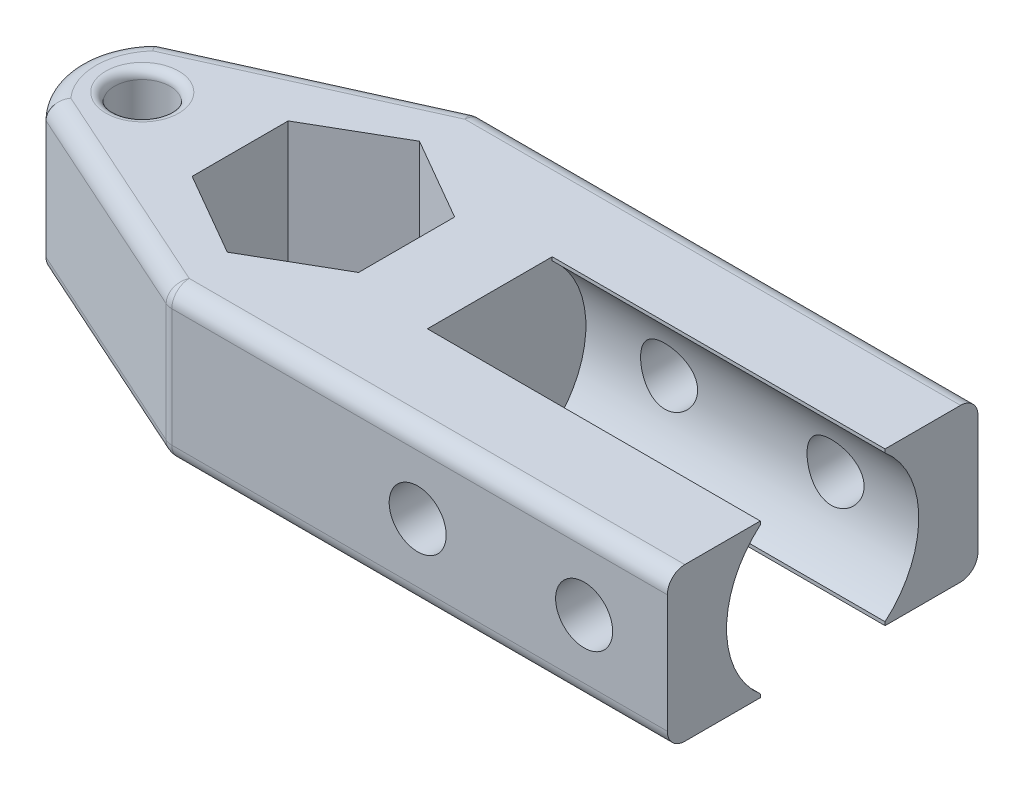
SolidWorks part; units mm, degrees
ref_plane "Front Plane" through (0, 0, 0) normal (0, 0, 1) x (1, 0, 0)
ref_plane "Top Plane" through (0, 0, 0) normal (0, 1, 0) x (1, 0, 0)
ref_plane "Right Plane" through (0, 0, 0) normal (1, 0, 0) x (0, 0, -1)
sketch "Sketch2" plane through (0, 0, 0) normal (0, 1, 0) x (1, 0, 0)
  line L0 (41.275, 0) -> (-41.275, 0) construction
  line L1 (31.75, -17.78) -> (-25.4, -17.78)
  line L3 (31.75, 17.78) -> (-25.4, 17.78)
  line L4 (-41.275, 0) -> (-60.325, 0) construction
  line L5 (41.275, -17.78) -> (-41.275, 17.78) construction
  line L6 (41.275, 17.78) -> (-41.275, -17.78) construction
  line L7 (-25.4, 17.78) -> (-25.4, -17.78) construction
  line L8 (31.75, 17.78) -> (31.75, -17.78)
  line L9 (-25.4, 10.9985) -> (-34.925, 5.4993)
  line L10 (-34.925, 5.4993) -> (-34.925, -5.4993)
  line L11 (-34.925, -5.4993) -> (-25.4, -10.9985)
  line L12 (-25.4, -10.9985) -> (-15.875, -5.4993)
  line L13 (-15.875, -5.4993) -> (-15.875, 5.4993)
  line L14 (-15.875, 5.4993) -> (-25.4, 10.9985)
  line L15 (-50.8, 6.35) -> (-25.4, 17.78)
  line L16 (-25.4, -17.78) -> (-50.8, -6.35)
  circle A0 centre (-25.4, 0) radius 9.525 construction
  arc A1 (-50.8, -6.35) -> (-50.8, 6.35) centre (-44.45, 0) cw
  circle A2 centre (-46.1277, 0) radius 3.175
  point P0 (0, 0)
  point P21 (-50.8, 0)
  dimension "D4" = 25.4
  dimension "D5" = 57.15
  dimension "D1" = 35.56
  dimension "D2" = 82.55
  dimension "D3" = 15.875
extrude "Boss-Extrude1" add sketch "Sketch2" along normal blind 17.526 contours A1 L16 L1 L3 L15 A2 region at (-3.1953, 0, 0)
fillet "Fillet4" radius 1 2 edges at (-46.1277, 0, 3.175) (-46.1277, 17.526, 3.175)
fillet "Fillet7" radius 2 6 edges at (-53.4303, 0, 0) (-38.1, 0, -12.065) (-38.1, 0, 12.065) (-38.1, 17.526, -12.065) (-53.4303, 17.526, 0) (-38.1, 17.526, 12.065)
sketch "Sketch5" plane through (31.75, 0, 0) normal (1, 0, 0) x (0, 0, -1)
  line L0 (-17.78, 8.763) -> (17.78, 8.763) construction
  line L1 (-17.78, 17.526) -> (-17.78, 0) construction
  line L2 (17.78, 17.526) -> (17.78, 0) construction
  line L3 (7.1438, 17.1276) -> (7.1438, 20.263)
  line L4 (7.1438, -2.737) -> (-7.1437, -2.737)
  line L5 (7.1438, -2.737) -> (7.1438, 0.3984)
  line L6 (7.1438, 20.263) -> (-7.1437, 20.263)
  line L7 (-7.1437, -2.737) -> (-7.1437, 0.3984)
  line L8 (7.1438, -2.737) -> (-7.1437, 20.263) construction
  line L9 (7.1438, 20.263) -> (-7.1437, -2.737) construction
  line L10 (-7.1437, 17.1276) -> (-7.1437, 20.263)
  arc A0 (-7.1437, 17.1276) -> (-7.1437, 0.3984) centre (0, 8.763) ccw
  arc A1 (7.1438, 0.3984) -> (7.1438, 17.1276) centre (0, 8.763) ccw
  dimension "D1" = 14.2875
  dimension "D2" = 11
extrude "Cut-Extrude3" cut sketch "Sketch5" against normal blind 38.1
sketch "Sketch6" plane through (0, 0, 17.78) normal (0, 0, 1) x (1, 0, 0)
  line L0 (31.75, 8.763) -> (-25.4, 8.763) construction
  line L1 (31.75, 17.526) -> (31.75, 0) construction
  line L2 (-25.4, 15.526) -> (-25.4, 2) construction
  circle A0 centre (3.175, 8.763) radius 3.2639
  circle A1 centre (22.225, 8.763) radius 3.2639
  dimension "D1" = 2
  dimension "D2" = 28.575
extrude "Cut-Extrude4" cut sketch "Sketch6" against normal through all
fillet "Fillet8" radius 2 10 edges at (5.6119, 0, -17.78) (-23.9725, 0.5858, -17.78) (-25.4, 8.763, -17.78) (-23.9725, 16.9402, -17.78) (5.6119, 0, 17.78) (-23.9725, 0.5858, 17.78) (-25.4, 8.763, 17.78) (-23.9725, 16.9402, 17.78) (5.6119, 17.526, -17.78) (5.6119, 17.526, 17.78)
